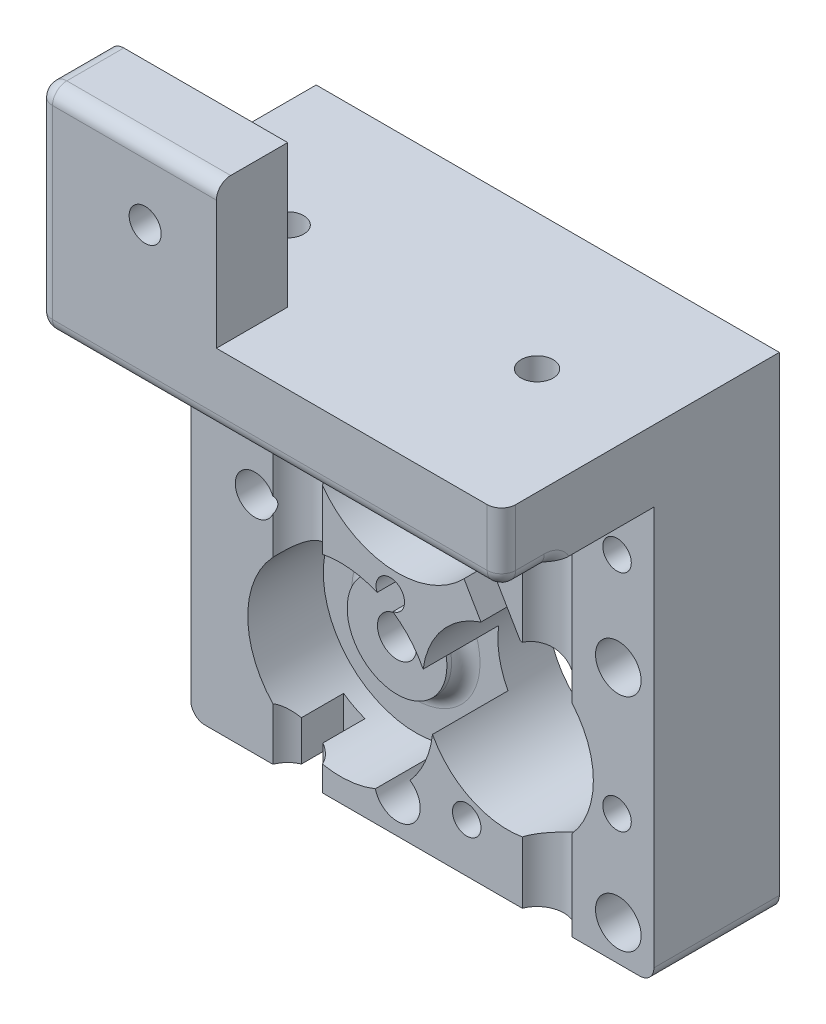
SolidWorks part; units mm, degrees
ref_plane "Front Plane" through (0, 0, 0) normal (0, 0, 1) x (1, 0, 0)
ref_plane "Top Plane" through (0, 0, 0) normal (0, 1, 0) x (1, 0, 0)
ref_plane "Right Plane" through (0, 0, 0) normal (1, 0, 0) x (0, 0, -1)
sketch "Sketch1" plane through (0, 0, 0) normal (0, 0, 1) x (1, 0, 0)
  line L1 (-44.5, 47.5) -> (20.5, 47.5)
  line L2 (-44.5, 47.5) -> (-44.5, -20.5)
  line L3 (-44.5, -20.5) -> (20.5, -20.5)
  line L4 (20.5, 47.5) -> (20.5, -20.5)
  circle A0 centre (0, 0) radius 12
  circle A1 centre (-15.5, 15.5) radius 1.75
  circle A2 centre (15.5, 15.5) radius 1.75
  circle A3 centre (15.5, -15.5) radius 1.75
  circle A4 centre (-15.5, -15.5) radius 1.75
  circle A6 centre (-15.5, 24.5) radius 2.75
  dimension "D1" = 24
  dimension "D2" = 31
  dimension "D3" = 31
  dimension "D4" = 31
  dimension "D5" = 31
  dimension "D6" = 15.5
  dimension "D7" = 15.5
  dimension "D8" = 0
  dimension "D9" = 3.5
  dimension "D10" = 3.5
  dimension "D11" = 3.5
  dimension "D12" = 3.5
  dimension "D13" = 23
  dimension "D14" = 29
  dimension "D16" = 5.5
  dimension "D21" = 47.5
  dimension "D22" = 44.5
  dimension "D19" = 65
  dimension "D20" = 68
extrude "Boss-Extrude1" add sketch "Sketch1" along normal blind 7
sketch "Sketch2" plane through (0, 0, 7) normal (0, 0, 1) x (1, 0, 0)
  line L0 (20.5, 47.5) -> (-44.5, 47.5) construction
  line L1 (-44.5, 47.5) -> (-44.5, -20.5) construction
  circle A0 centre (-15.5, 24.5) radius 2.75
  circle A6 centre (-35.5, 11) radius 2.75
  circle A8 centre (-23.5, -4.2471) radius 2.75
  circle A9 centre (-23.5, -4.2471) radius 7
  circle A10 centre (-15.5, 24.5) radius 7
  circle A11 centre (-35.5, 11) radius 4
  dimension "D1" = 14
  dimension "D2" = 5.5
  dimension "D3" = 5.5
  dimension "D4" = 8
  dimension "D6" = 14
  dimension "D5" = 23
  dimension "D8" = 29
  dimension "D9" = 36.5
  dimension "D10" = 9
  dimension "D11" = 51.7471
  dimension "D7" = 21
extrude "Boss-Extrude2" add sketch "Sketch2" along normal blind 2.65
sketch "Sketch3" plane through (20.5, 0, 0) normal (1, 0, 0) x (0, 0, -1)
  line L1 (-7, 47.5) -> (-29, 47.5)
  line L2 (-7, 47.5) -> (-7, 37.5)
  line L3 (-7, 37.5) -> (-29, 37.5)
  line L4 (-29, 47.5) -> (-29, 37.5)
  line L5 (-29, 37.5) -> (-39, 37.5)
  line L6 (-29, 37.5) -> (-29, 67.5)
  line L7 (-29, 67.5) -> (-39, 67.5)
  line L8 (-39, 37.5) -> (-39, 67.5)
  line M7 (-7, 47.5) -> (-7, -20.5)
  dimension "D1" = 22
  dimension "D2" = 10
  dimension "D3" = 20
  dimension "D4" = 10
extrude "Boss-Extrude3" add sketch "Sketch3" against normal through all contours L1 L4 L3 M7 | L8 L5 L4 L6 L7 region at (20.5, 42.5, 18) region at (20.5, 52.5, 34)
sketch "Sketch4" plane through (0, 0, 39) normal (0, 0, 1) x (1, 0, 0)
  line L0 (-44.5, 37.5) -> (20.5, 37.5) construction
  line L1 (-44.5, 67.5) -> (20.5, 67.5) construction
  line L2 (-44.5, 37.5) -> (-44.5, 67.5) construction
  line L3 (20.5, 37.5) -> (20.5, 67.5) construction
  circle A0 centre (-29.5, 57.5) radius 2.25
  circle A1 centre (5.5, 57.5) radius 2.25
  dimension "D1" = 4.5
  dimension "D2" = 20
  dimension "D3" = 10
  dimension "D4" = 15
  dimension "D5" = 10
  dimension "D6" = 15
  dimension "D7" = 4.5
extrude "Cut-Extrude1" cut sketch "Sketch4" against normal blind 10
sketch "Sketch5" plane through (0, 37.5, 0) normal (0, -1, 0) x (1, 0, 0)
  line L0 (-44.5, 7) -> (-44.5, 39) construction
  line L1 (-44.5, 39) -> (20.5, 39) construction
  line L2 (20.5, 7) -> (20.5, 39) construction
  circle A0 centre (-29.5, 19) radius 2.25
  circle A1 centre (5.5, 19) radius 2.25
  dimension "D1" = 15
  dimension "D2" = 20
  dimension "D3" = 20
  dimension "D4" = 15
  dimension "D5" = 4.5
  dimension "D6" = 4.5
extrude "Cut-Extrude2" cut sketch "Sketch5" against normal blind 10
sketch "Sketch7" plane through (0, 0, 0) normal (0, 0, -1) x (-1, 0, 0)
  line L1 (-20.5, -20.5) -> (20.5, -20.5)
  line L2 (-20.5, -20.5) -> (-20.5, 20.5)
  line L3 (-20.5, 20.5) -> (20.5, 20.5)
  line L4 (20.5, -20.5) -> (20.5, 20.5)
  circle A0 centre (0, 0) radius 12
  circle A1 centre (-15.5, 15.5) radius 1.75
  circle A2 centre (15.5, 15.5) radius 1.75
  circle A3 centre (15.5, -15.5) radius 1.75
  circle A4 centre (-15.5, -15.5) radius 1.75
  dimension "D2" = 5
  dimension "D3" = 5
  dimension "D4" = 5
  dimension "D1" = 5
extrude "Boss-Extrude5" add sketch "Sketch7" along normal blind 5.9
sketch "Sketch8" plane through (0, 0, 9.65) normal (0, 0, 1) x (1, 0, 0)
  circle A0 centre (-35.5, 11) radius 2.75
  circle A1 centre (-35.5, 11) radius 4
  dimension "D1" = 8
extrude "Boss-Extrude6" add sketch "Sketch8" along normal blind 7.95
sketch "Sketch10" plane through (0, 0, 7) normal (0, 0, 1) x (1, 0, 0)
  circle A0 centre (-35.5, 11) radius 2.75
  circle A1 centre (-23.5, -4.2471) radius 2.75
extrude "Cut-Extrude3" cut sketch "Sketch10" against normal blind 9.45
sketch "Sketch11" plane through (0, 0, 7) normal (0, 0, 1) x (1, 0, 0)
  line L1 (-44.5, 37.5) -> (20.5, 37.5)
  line L2 (-44.5, 37.5) -> (-44.5, -20.5)
  line L3 (-44.5, -20.5) -> (20.5, -20.5)
  line L4 (20.5, 37.5) -> (20.5, -20.5)
  circle A0 centre (-23.5, -4.2471) radius 10
  circle A1 centre (-15.5, 24.5) radius 10
  circle A2 centre (-15.5, 24.5) radius 2.75
  circle A3 centre (-23.5, -4.2471) radius 2.75
  circle A4 centre (0, 0) radius 7.25
  circle M1 centre (15.5, -15.5) radius 1.75
  circle M2 centre (-15.5, 15.5) radius 1.75
  circle M3 centre (0, 0) radius 12
  circle M4 centre (15.5, 15.5) radius 1.75
  circle M5 centre (-15.5, -15.5) radius 1.75
  circle M7 centre (-35.5, 11) radius 4
  line M9 (20.5, -20.5) -> (20.5, 37.5)
  line M10 (20.5, 37.5) -> (-44.5, 37.5)
  line M11 (-44.5, 37.5) -> (-44.5, -20.5)
  line M12 (-44.5, -20.5) -> (20.5, -20.5)
  dimension "D1" = 20
  dimension "D2" = 20
  dimension "D3" = 14.5
extrude "Boss-Extrude7" add sketch "Sketch11" along normal blind 10 contours A1 A0 M12 M9 M10 M11 M2 M4 M7 M5 M3 M1 | A4 M3 region at (-12.0095, 9.6819, 7) region at (-11.6606, 0, 7)
sketch "Sketch12" plane through (0, 0, 17) normal (0, 0, 1) x (1, 0, 0)
  line L1 (-11.6164, 26.7733) -> (3.0206, 1.7681)
  line L2 (-44.5, 37.5) -> (-44.5, -20.5) construction
  line L6 (-44.5, -20.5) -> (20.5, -20.5) construction
  line L7 (-44.5, 29) -> (-15.5, 29)
  line L8 (-44.5, 29) -> (-44.5, 32)
  line L9 (-44.5, 32) -> (-15.5, 32)
  line L13 (-9.0274, 28.2888) -> (5.6096, 3.2836)
  line L14 (-21.2843, 2.9181) -> (-1.034, -3.3438)
  line L17 (-22.1706, 0.052) -> (-1.9202, -6.2099)
  line L18 (-31, -4.2471) -> (-31, -20.5)
  line L20 (-31, -20.5) -> (-28, -20.5)
  line L21 (-28, -4.2471) -> (-28, -20.5)
  arc A5 (-21.2843, 2.9181) -> (-31, -4.2471) centre (-23.5, -4.2471) ccw
  arc A6 (-22.1706, 0.052) -> (-28, -4.2471) centre (-23.5, -4.2471) ccw
  arc A7 (-1.034, -3.3438) -> (3.0206, 1.7681) centre (0, 0) ccw
  arc A8 (-11.6164, 26.7733) -> (-15.5, 29) centre (-15.5, 24.5) ccw
  arc A9 (-9.0274, 28.2888) -> (-15.5, 32) centre (-15.5, 24.5) ccw
  arc A10 (-1.9202, -6.2099) -> (5.6096, 3.2836) centre (0, 0) ccw
  dimension "D4" = 3
  dimension "D5" = 3
  dimension "D6" = 3
  dimension "D7" = 3
extrude "Cut-Extrude4" cut sketch "Sketch12" against normal up to surface (7.35 mm away) up to face at (-16.5, -4.2471, 9.65)
sketch "Sketch13" plane through (0, 0, 17) normal (0, 0, 1) x (1, 0, 0)
  line L0 (-44.5, 29) -> (-44.5, -20.5) construction
  line L1 (-15.5, 34.5) -> (-44.5, 34.5)
  line L3 (-15.5, 14.5) -> (-44.5, 14.5)
  line L4 (-44.5, 34.5) -> (-44.5, 14.5)
  line L11 (-23.5, 5.7529) -> (-44.5, 5.7529)
  line L13 (-23.5, -14.2471) -> (-44.5, -14.2471)
  line L14 (-44.5, 5.7529) -> (-44.5, -14.2471)
  arc A0 (-15.5, 14.5) -> (-15.5, 34.5) centre (-15.5, 24.5) ccw
  circle A1 centre (-15.5, 24.5) radius 7
  circle A2 centre (-23.5, -4.2471) radius 7
  arc A4 (-23.5, -14.2471) -> (-23.5, 5.7529) centre (-23.5, -4.2471) ccw
extrude "Cut-Extrude5" cut sketch "Sketch13" against normal up to surface (10 mm away) up to face at (-15.5, 25.875, 7)
sketch "Sketch14" plane through (0, 0, 17) normal (0, 0, 1) x (1, 0, 0)
  circle A0 centre (15.5, 15.5) radius 3
  circle A1 centre (15.5, -15.5) radius 3
  circle A2 centre (-15.5, -15.5) radius 3
  circle A3 centre (-15.5, 15.5) radius 3
  dimension "D1" = 6
extrude "Cut-Extrude6" cut sketch "Sketch14" against normal blind 17
sketch "Sketch15" plane through (0, 0, 17) normal (0, 0, 1) x (1, 0, 0)
  line L0 (-44.5, 37.5) -> (20.5, 37.5)
  line L1 (20.5, 37.5) -> (20.5, -20.5)
  line L8 (-26.9872, 5.7529) -> (-23.5, 5.7529)
  line L9 (-26.1325, 14.5) -> (-18.3284, 14.5)
  line L10 (-15.5, 34.5) -> (-44.5, 34.5)
  line L11 (-44.5, 34.5) -> (-44.5, 37.5)
  line L12 (-14.9652, 0.9641) -> (-7.0998, -1.4681)
  line L13 (-4.9882, -5.2612) -> (-13.6389, -2.5862)
  line L14 (3.9873, 6.055) -> (-5.686, 22.5805)
  line L15 (-7.1051, 19.0663) -> (-0.1869, 7.2476)
  line L18 (-28, -20.5) -> (-28, -14.2471)
  line L19 (-28, -14.2471) -> (-23.5, -14.2471)
  line L21 (-44.5, -20.5) -> (-31, -20.5)
  line L22 (-44.5, -20.5) -> (-44.5, -14.2471)
  line L23 (-44.5, -14.2471) -> (-31, -14.2471)
  line L24 (-31, -20.5) -> (-31, -14.2471)
  line L25 (-28, -20.5) -> (20.5, -20.5)
  arc A0 (-12.5519, 14.9444) -> (-7.1051, 19.0663) centre (-15.5, 24.5) ccw
  arc A1 (-18.3284, 14.5) -> (-12.5519, 14.9444) centre (-15.5, 15.5) ccw
  arc A4 (-4.9882, -5.2612) -> (3.9873, 6.055) centre (0, 0) ccw
  circle A5 centre (15.5, 15.5) radius 3
  circle A6 centre (15.5, -15.5) radius 3
  arc A8 (-0.1869, 7.2476) -> (-7.0998, -1.4681) centre (0, 0) ccw
  arc A12 (-5.686, 22.5805) -> (-15.5, 34.5) centre (-15.5, 24.5) ccw
  circle A15 centre (-15.5, -15.5) radius 3
  arc A18 (-14.9652, 0.9641) -> (-23.5, 5.7529) centre (-23.5, -4.2471) ccw
  arc A19 (-26.9872, 5.7529) -> (-26.1325, 14.5) centre (-35.5, 11) ccw
  arc A20 (-23.5, -14.2471) -> (-13.6389, -2.5862) centre (-23.5, -4.2471) ccw
extrude "Boss-Extrude9" add sketch "Sketch15" along normal blind 3.5
sketch "Sketch16" plane through (0, 0, 20.5) normal (0, 0, 1) x (1, 0, 0)
  line L1 (-44.5, 37.5) -> (20.5, 37.5)
  line L2 (-44.5, 37.5) -> (-44.5, -20.5)
  line L3 (-44.5, -20.5) -> (20.5, -20.5)
  line L4 (20.5, 37.5) -> (20.5, -20.5)
  arc A0 (-44.5, 6.6411) -> (-44.5, 15.3589) centre (-35.5, 11) ccw
  circle A1 centre (-15.5, 15.5) radius 3
  circle A2 centre (15.5, 15.5) radius 3
  circle A3 centre (15.5, -15.5) radius 3
  circle A4 centre (-15.5, -15.5) radius 3
  circle M1 centre (15.5, -15.5) radius 3
  line M2 (-44.5, 37.5) -> (-44.5, 34.5)
  line M3 (-44.5, 34.5) -> (-15.5, 34.5)
  arc M4 (-15.5, 34.5) -> (-5.686, 22.5805) centre (-15.5, 24.5) cw
  line M5 (-5.686, 22.5805) -> (3.9873, 6.055)
  arc M6 (3.9873, 6.055) -> (-4.9882, -5.2612) centre (0, 0) cw
  line M7 (-4.9882, -5.2612) -> (-13.6389, -2.5862)
  arc M8 (-13.6389, -2.5862) -> (-23.5, -14.2471) centre (-23.5, -4.2471) cw
  line M9 (-23.5, -14.2471) -> (-28, -14.2471)
  line M10 (-28, -14.2471) -> (-28, -20.5)
  line M11 (-28, -20.5) -> (20.5, -20.5)
  line M12 (20.5, -20.5) -> (20.5, 37.5)
  line M13 (20.5, 37.5) -> (7.1771, 37.5)
  line M14 (7.1771, 37.5) -> (3.8229, 37.5)
  line M15 (3.8229, 37.5) -> (-27.8229, 37.5)
  line M16 (-27.8229, 37.5) -> (-31.1771, 37.5)
  line M17 (-31.1771, 37.5) -> (-44.5, 37.5)
  circle M18 centre (15.5, 15.5) radius 3
  circle M19 centre (-15.5, -15.5) radius 3
extrude "Boss-Extrude10" add sketch "Sketch16" along normal blind 7.5 contours A0 L2 L3 A1 M10 M9 M8 M7 M6 M5 M4 M3 | M17 M2 M3 M4 M5 M6 M7 M8 M9 M10 M11 M12 M13 M14 M15 M16 M19 M18 M1 region at (2.7798, 8.7673, 20.5) region at (-21.9314, 8.3685, 20.5)
sketch "Sketch17" plane through (0, 0, 28) normal (0, 0, 1) x (1, 0, 0)
  line L1 (-44.5, 37.5) -> (20.5, 37.5)
  line L2 (-44.5, 37.5) -> (-44.5, -20.5)
  line L3 (-44.5, -20.5) -> (20.5, -20.5)
  line L4 (20.5, 37.5) -> (20.5, -20.5)
  circle A0 centre (-15.5, 15.5) radius 3
  circle A1 centre (15.5, 15.5) radius 3
  circle A2 centre (15.5, -15.5) radius 3
  circle A3 centre (-15.5, -15.5) radius 3
extrude "Boss-Extrude11" add sketch "Sketch17" along normal blind 3
sketch "Sketch18" plane through (0, 47.5, 0) normal (0, 1, 0) x (1, 0, 0)
  circle A0 centre (-29.5, -19) radius 2.25
  circle A1 centre (5.5, -19) radius 2.25
extrude "Cut-Extrude7" cut sketch "Sketch18" against normal through all
sketch "Sketch19" plane through (0, -20.5, 0) normal (0, -1, 0) x (1, 0, 0)
  circle A0 centre (-29.5, 19) radius 3.75
  circle A1 centre (5.5, 19) radius 3.75
  dimension "D1" = 7.5
  dimension "D2" = 7.5
extrude "Cut-Extrude8" cut sketch "Sketch19" against normal blind 58
fillet "Fillet2" radius 2 14 edges at (20.5, 37.5, 35) (-44.5, 37.5, 35) (-44.5, 67.5, 34) (20.5, 67.5, 34) (-12, 67.5, 39) (20.5, 52.5, 39) (-44.5, 52.5, 39) (-12, 37.5, 31) (-12, 37.5, 39) (20.5, 8.5, 31) (20.5, -20.5, 12.55) (-12, -20.5, 31) (-44.5, -20.5, 15.5) (-44.5, 8.5, 31)
sketch "Sketch20" plane through (0, 0, 0) normal (0, 0, -1) x (-1, 0, 0)
  line L0 (20.5, 20.5) -> (-20.5, 20.5) construction
  line L1 (13.1906, 28.5) -> (10.8812, 24.5)
  line L2 (10.8812, 24.5) -> (13.1906, 20.5)
  line L3 (13.1906, 20.5) -> (17.8094, 20.5)
  line L4 (17.8094, 20.5) -> (20.1188, 24.5)
  line L5 (20.1188, 24.5) -> (17.8094, 28.5)
  line L6 (17.8094, 28.5) -> (13.1906, 28.5)
  line L7 (39.5, 13.3094) -> (35.5, 15.6188)
  line L8 (35.5, 15.6188) -> (31.5, 13.3094)
  line L9 (31.5, 13.3094) -> (31.5, 8.6906)
  line L10 (31.5, 8.6906) -> (35.5, 6.3812)
  line L11 (35.5, 6.3812) -> (39.5, 8.6906)
  line L12 (39.5, 8.6906) -> (39.5, 13.3094)
  line L13 (23.5, 0.3717) -> (19.5, -1.9377)
  line L14 (19.5, -1.9377) -> (19.5, -6.5565)
  line L15 (19.5, -6.5565) -> (23.5, -8.8659)
  line L16 (23.5, -8.8659) -> (27.5, -6.5565)
  line L17 (27.5, -6.5565) -> (27.5, -1.9377)
  line L18 (27.5, -1.9377) -> (23.5, 0.3717)
  line L19 (20.5, -20.5) -> (20.5, 20.5) construction
  line L20 (20.5, -20.5) -> (20.5, 20.5) construction
  circle A0 centre (15.5, 24.5) radius 4 construction
  circle A1 centre (35.5, 11) radius 4 construction
  circle A2 centre (23.5, -4.2471) radius 4 construction
  point P33 (33.5, 14.4641)
  dimension "D1" = 8
extrude "Cut-Extrude9" cut sketch "Sketch20" against normal blind 5.5
sketch "Sketch21" plane through (0, 0, 0) normal (0, 0, -1) x (-1, 0, 0)
  line L1 (17.9537, 28.75) -> (13.0463, 28.75)
  line L2 (13.0463, 28.75) -> (10.5925, 24.5)
  line L3 (10.5925, 24.5) -> (13.0463, 20.25)
  line L4 (13.0463, 20.25) -> (17.9537, 20.25)
  line L5 (17.9537, 20.25) -> (20.4075, 24.5)
  line L6 (20.4075, 24.5) -> (17.9537, 28.75)
  line L7 (27.75, -1.7934) -> (23.5, 0.6603)
  line L8 (23.5, 0.6603) -> (19.25, -1.7934)
  line L9 (19.25, -1.7934) -> (19.25, -6.7009)
  line L10 (19.25, -6.7009) -> (23.5, -9.1546)
  line L11 (23.5, -9.1546) -> (27.75, -6.7009)
  line L12 (27.75, -6.7009) -> (27.75, -1.7934)
  circle A0 centre (15.5, 24.5) radius 4.25 construction
  circle A1 centre (23.5, -4.2471) radius 4.25 construction
extrude "Cut-Extrude10" cut sketch "Sketch21" along normal blind 29.5
sketch "Sketch22" plane through (0, 0, 39) normal (0, 0, 1) x (1, 0, 0)
  line L0 (-44.5, 35.5) -> (-44.5, -20.5) construction
  line L1 (18.5, -20.5) -> (-44.5, -20.5) construction
  line L2 (20.5, 35.5) -> (20.5, 39.5) construction
  line L3 (-44.5, -20.5) -> (20.5, -20.5)
  line L4 (-44.5, -20.5) -> (-44.5, 37.5)
  line L5 (-44.5, 37.5) -> (20.5, 37.5)
  line L6 (20.5, -20.5) -> (20.5, 37.5)
extrude "Cut-Extrude11" cut sketch "Sketch22" against normal up to surface (21.4 mm away) up to face at (-35.9269, 11, 17.6)
sketch "Sketch23" plane through (0, 0, 17.6) normal (0, 0, 1) x (1, 0, 0)
  line L0 (20.5, 37.5) -> (20.5, -18.5) construction
  circle A0 centre (-5.7708, -13.6227) radius 1.8
  circle A1 centre (-16.5, 8.4364) radius 1.8
  circle A2 centre (15.3222, 29.1269) radius 1.8
  circle A3 centre (15.3222, -2.3516) radius 1.8
  dimension "D1" = 3.6
  dimension "D2" = 37
extrude "Cut-Extrude12" cut sketch "Sketch23" against normal blind 10
sketch "Sketch24" plane through (0, 0, 17.6) normal (0, 0, 1) x (1, 0, 0)
  circle A0 centre (-16.5, 8.4364) radius 2
  circle A1 centre (15.3222, 29.1269) radius 2
  circle A2 centre (15.3222, -2.3516) radius 2
  circle A3 centre (-5.7708, -13.6227) radius 2
  dimension "D1" = 4
extrude "Cut-Extrude13" cut sketch "Sketch24" against normal blind 4
sketch "Sketch26" plane through (0, 0, -5.9) normal (0, 0, -1) x (-1, 0, 0)
  line L1 (-20.5, 20.5) -> (20.5, 20.5)
  line L2 (-20.5, 20.5) -> (-20.5, -20.5)
  line L3 (-20.5, -20.5) -> (20.5, -20.5)
  line L4 (20.5, 20.5) -> (20.5, -20.5)
extrude "Cut-Extrude14" cut sketch "Sketch26" against normal up to surface (5.9 mm away) up to face at (-18.2276, 9.3731, 0)
sketch "Sketch27" plane through (0, 0, 17) normal (0, 0, 1) x (1, 0, 0)
  line L1 (-44.5, 14.5) -> (-18.3284, 14.5)
  line L2 (-44.5, 14.5) -> (-44.5, 30.5)
  line L3 (-44.5, 30.5) -> (-23.5, 30.5)
  line L5 (-44.5, 34.5) -> (-32.9789, 34.5) construction
  line L6 (-31, -14.2471) -> (-31, -10.8615)
  line L7 (-44.5, -14.2471) -> (-31, -14.2471)
  line L8 (-44.5, -14.2471) -> (-44.5, 5.7529)
  line L9 (-44.5, 5.7529) -> (-23.5, 5.7529)
  arc A0 (-23.5, 5.7529) -> (-31, -10.8615) centre (-23.5, -4.2471) ccw
  arc A1 (-23.5, 30.5) -> (-18.4481, 14.9444) centre (-15.5, 24.5) ccw
  arc A2 (-18.4481, 14.9444) -> (-18.3284, 14.5) centre (-15.5, 15.5) ccw
  dimension "D1" = 4
extrude "Boss-Extrude12" add sketch "Sketch27" against normal up to surface (10 mm away) and the other way up to surface (0.6 mm away) up to face at (-31.5, -4.2471, 7) other way up to face at (-35.9269, 11, 17.6)
sketch "Sketch29" plane through (0, 0, 17) normal (0, 0, 1) x (1, 0, 0)
  line L0 (-33.5635, 14.5) -> (-32.6721, 14.5)
  line L1 (-44.5, 5.7529) -> (-32.6721, 5.7529)
  line L2 (-44.5, 5.7529) -> (-44.5, 14.5)
  line L3 (-44.5, 14.5) -> (-37.4365, 14.5)
  line L4 (-32.6721, 5.7529) -> (-32.6721, 8.171)
  line L5 (-26.3279, 14.5) -> (-26.1325, 14.5)
  line L6 (-26.3279, 14.5) -> (-26.3279, 7.0161)
  line L9 (-32.6721, 13.829) -> (-32.6721, 14.5)
  arc A0 (-37.4365, 14.5) -> (-32.6721, 8.171) centre (-35.5, 11) ccw
  arc A1 (-26.3279, 7.0161) -> (-26.1325, 14.5) centre (-35.5, 11) ccw
  arc A2 (-32.6721, 13.829) -> (-33.5635, 14.5) centre (-35.5, 11) ccw
extrude "Boss-Extrude13" add sketch "Sketch29" along normal up to surface (0.6 mm away) up to face at (-29.2401, 6.0247, 17.6)
sketch "Sketch28" plane through (0, -20.5, 0) normal (0, -1, 0) x (1, 0, 0)
  circle A0 centre (-29.5, 19) radius 3.75
extrude "Cut-Extrude15" cut sketch "Sketch28" against normal up to surface (58 mm away) up to face at (-29.5, 37.5, 16.75)
ref_plane "Plane2" through (0, 0, 27.6) normal (0, 0, 1) x (1, 0, 0)
sketch "Sketch31" plane through (0, 0, 27.6) normal (0, 0, 1) x (1, 0, 0)
  line L0 (-44.5, 34.5) -> (-32.9789, 34.5) construction
  line L1 (-32.9789, 34.5) -> (-32.9789, 37.5) construction
  line L2 (-32.9789, 37.5) -> (-44.5, 37.5) construction
  line L3 (-44.5, 37.5) -> (-44.5, 34.5) construction
  line L4 (-26.0211, 30.5) -> (-26.0211, 5.4298) construction
  line L5 (-14.9652, 0.9641) -> (-7.0998, -1.4681) construction
  line L6 (-0.1869, 7.2476) -> (-7.1051, 19.0663) construction
  line L7 (-23.5, 30.5) -> (-26.0211, 30.5) construction
  line L8 (-26.0211, 37.5) -> (-26.0211, 34.5) construction
  line L9 (-26.0211, 34.5) -> (-15.5, 34.5) construction
  line L10 (-5.686, 22.5805) -> (2.0211, 9.414) construction
  line L11 (2.0211, 9.414) -> (2.0211, 37.5) construction
  line L12 (2.0211, 37.5) -> (-26.0211, 37.5) construction
  line L13 (8.9789, 37.5) -> (8.9789, -20.5) construction
  line L14 (8.9789, -20.5) -> (18.5, -20.5) construction
  line L15 (20.5, -18.5) -> (20.5, 37.5) construction
  line L16 (20.5, 37.5) -> (8.9789, 37.5) construction
  line L17 (-26.0211, -14.2471) -> (-26.0211, -20.5) construction
  line L18 (-26.0211, -20.5) -> (2.0211, -20.5) construction
  line L19 (2.0211, -20.5) -> (2.0211, -6.9626) construction
  line L20 (-4.9882, -5.2612) -> (-13.6389, -2.5862) construction
  line L21 (-23.5, -14.2471) -> (-26.0211, -14.2471) construction
  line L22 (-32.9789, 12.0984) -> (-32.9789, 30.5) construction
  line L23 (-32.9789, 30.5) -> (-44.5, 30.5) construction
  line L24 (-44.5, 30.5) -> (-44.5, -18.5) construction
  line L25 (-42.5, -20.5) -> (-32.9789, -20.5) construction
  line L26 (-32.9789, -20.5) -> (-32.9789, -7.4332) construction
  line L27 (-32.9789, -1.0611) -> (-32.9789, 9.9016) construction
  line L28 (-44.5, 34.5) -> (-32.9789, 34.5)
  line L29 (-32.9789, 34.5) -> (-32.9789, 37.5)
  line L30 (-32.9789, 37.5) -> (-44.5, 37.5)
  line L31 (-44.5, 37.5) -> (-44.5, 34.5)
  line L32 (-26.0211, 30.5) -> (-26.0211, 5.4298)
  line L33 (-14.9652, 0.9641) -> (-7.0998, -1.4681)
  line L34 (-0.1869, 7.2476) -> (-7.1051, 19.0663)
  line L35 (-23.5, 30.5) -> (-26.0211, 30.5)
  line L36 (-26.0211, 37.5) -> (-26.0211, 34.5)
  line L37 (-26.0211, 34.5) -> (-15.5, 34.5)
  line L38 (-5.686, 22.5805) -> (2.0211, 9.414)
  line L39 (2.0211, 9.414) -> (2.0211, 37.5)
  line L40 (2.0211, 37.5) -> (-26.0211, 37.5)
  line L41 (8.9789, 37.5) -> (8.9789, -20.5)
  line L42 (8.9789, -20.5) -> (18.5, -20.5)
  line L43 (20.5, -18.5) -> (20.5, 37.5)
  line L44 (20.5, 37.5) -> (8.9789, 37.5)
  line L45 (-26.0211, -14.2471) -> (-26.0211, -20.5)
  line L46 (-26.0211, -20.5) -> (2.0211, -20.5)
  line L47 (2.0211, -20.5) -> (2.0211, -6.9626)
  line L48 (-4.9882, -5.2612) -> (-13.6389, -2.5862)
  line L49 (-23.5, -14.2471) -> (-26.0211, -14.2471)
  line L50 (-32.9789, 12.0984) -> (-32.9789, 30.5)
  line L51 (-32.9789, 30.5) -> (-44.5, 30.5)
  line L52 (-44.5, 30.5) -> (-44.5, -18.5)
  line L53 (-42.5, -20.5) -> (-32.9789, -20.5)
  line L54 (-32.9789, -20.5) -> (-32.9789, -7.4332)
  line L55 (-32.9789, -1.0611) -> (-32.9789, 9.9016)
  arc A0 (-14.9652, 0.9641) -> (-26.0211, 5.4298) centre (-23.5, -4.2471) ccw construction
  arc A1 (-0.1869, 7.2476) -> (-7.0998, -1.4681) centre (0, 0) ccw construction
  arc A2 (-12.5519, 14.9444) -> (-7.1051, 19.0663) centre (-15.5, 24.5) ccw construction
  arc A3 (-18.4481, 14.9444) -> (-12.5519, 14.9444) centre (-15.5, 15.5) ccw construction
  arc A4 (-23.5, 30.5) -> (-18.4481, 14.9444) centre (-15.5, 24.5) ccw construction
  arc A5 (-5.686, 22.5805) -> (-15.5, 34.5) centre (-15.5, 24.5) ccw construction
  arc A6 (18.5, -20.5) -> (20.5, -18.5) centre (18.5, -18.5) ccw construction
  arc A7 (-4.9882, -5.2612) -> (2.0211, -6.9626) centre (0, 0) ccw construction
  arc A8 (-23.5, -14.2471) -> (-13.6389, -2.5862) centre (-23.5, -4.2471) ccw construction
  arc A9 (-44.5, -18.5) -> (-42.5, -20.5) centre (-42.5, -18.5) ccw construction
  arc A10 (-32.9789, -1.0611) -> (-32.9789, -7.4332) centre (-23.5, -4.2471) ccw construction
  arc A11 (-32.9789, 12.0984) -> (-32.9789, 9.9016) centre (-35.5, 11) ccw construction
  circle A12 centre (-5.7708, -13.6227) radius 2 construction
  circle A13 centre (-16.5, 8.4364) radius 2 construction
  circle A14 centre (15.3222, 29.1269) radius 2 construction
  circle A15 centre (15.3222, -2.3516) radius 2 construction
  arc A16 (-14.9652, 0.9641) -> (-26.0211, 5.4298) centre (-23.5, -4.2471) ccw
  arc A17 (-0.1869, 7.2476) -> (-7.0998, -1.4681) centre (0, 0) ccw
  arc A18 (-12.5519, 14.9444) -> (-7.1051, 19.0663) centre (-15.5, 24.5) ccw
  arc A19 (-18.4481, 14.9444) -> (-12.5519, 14.9444) centre (-15.5, 15.5) ccw
  arc A20 (-23.5, 30.5) -> (-18.4481, 14.9444) centre (-15.5, 24.5) ccw
  arc A21 (-5.686, 22.5805) -> (-15.5, 34.5) centre (-15.5, 24.5) ccw
  arc A22 (18.5, -20.5) -> (20.5, -18.5) centre (18.5, -18.5) ccw
  arc A23 (-4.9882, -5.2612) -> (2.0211, -6.9626) centre (0, 0) ccw
  arc A24 (-23.5, -14.2471) -> (-13.6389, -2.5862) centre (-23.5, -4.2471) ccw
  arc A25 (-44.5, -18.5) -> (-42.5, -20.5) centre (-42.5, -18.5) ccw
  arc A26 (-32.9789, -1.0611) -> (-32.9789, -7.4332) centre (-23.5, -4.2471) ccw
  arc A27 (-32.9789, 12.0984) -> (-32.9789, 9.9016) centre (-35.5, 11) ccw
  circle A28 centre (-5.7708, -13.6227) radius 2
  circle A29 centre (-16.5, 8.4364) radius 2
  circle A30 centre (15.3222, 29.1269) radius 2
  circle A31 centre (15.3222, -2.3516) radius 2
sketch "Sketch32" plane through (0, 0, 7) normal (0, 0, -1) x (-1, 0, 0)
  circle A0 centre (-15.5, 15.5) radius 3.2
  circle A1 centre (15.5, 15.5) radius 3.2
  circle A2 centre (15.5, -15.5) radius 3.2
  circle A3 centre (-15.5, -15.5) radius 3.2
  dimension "D1" = 6.4
extrude "Cut-Extrude16" cut sketch "Sketch32" against normal blind 14 and the other way blind 10
sketch "Sketch34" plane through (0, 0, 7) normal (0, 0, 1) x (1, 0, 0)
  circle A0 centre (-15.5, 24.5) radius 7
  circle A1 centre (-15.5, 24.5) radius 11
  circle A2 centre (-23.5, -4.2471) radius 7
  circle A3 centre (-23.5, -4.2471) radius 11
  dimension "D1" = 22
  dimension "D2" = 22
extrude "Cut-Extrude17" cut sketch "Sketch34" along normal up to surface (10.6 mm away) up to face at (-37.2866, 1.6213, 17.6)
sketch "Sketch35" plane through (0, 0, 7) normal (0, 0, -1) x (-1, 0, 0)
  circle A0 centre (0, 0) radius 12
extrude "Cut-Extrude18" cut sketch "Sketch35" against normal through all
fillet "Fillet4" radius 2 2 edges at (-16.5, -4.2471, 7) (-15.5, 31.5, 7)
sketch "Sketch36" plane through (0, 0, 0) normal (0, 0, -1) x (-1, 0, 0)
  circle A0 centre (-15.5, 15.5) radius 3.2
  circle A1 centre (-15.5, 15.5) radius 1.8
  circle A2 centre (15.5, 15.5) radius 3.2
  circle A3 centre (15.5, 15.5) radius 1.8
  circle A4 centre (15.5, -15.5) radius 3.2
  circle A5 centre (15.5, -15.5) radius 1.8
  circle A6 centre (-15.5, -15.5) radius 3.2
  circle A7 centre (-15.5, -15.5) radius 1.8
  dimension "D1" = 3.6
  dimension "D2" = 2
  dimension "D3" = 2
extrude "Boss-Extrude14" add sketch "Sketch36" against normal blind 6.5
sketch "Sketch37" plane through (0, 0, 29) normal (0, 0, -1) x (-1, 0, 0)
  line L0 (42.5, 67.5) -> (-18.5, 67.5) construction
  line L1 (-20.5, 47.5) -> (19.5, 47.5)
  line L2 (-20.5, 47.5) -> (-20.5, 67.5)
  line L3 (-20.5, 67.5) -> (19.5, 67.5)
  line L4 (19.5, 47.5) -> (19.5, 67.5)
  dimension "D1" = 40
extrude "Cut-Extrude19" cut sketch "Sketch37" against normal through all
sketch "Sketch38" plane through (0, 0, 17.6) normal (0, 0, 1) x (1, 0, 0)
  line L2 (-44.5, 34.5) -> (-44.5, 35.5)
  line L3 (-44.5, 35.5) -> (-22.4282, 35.5)
  line L6 (-44.5, 30.5) -> (-44.5, 29.5)
  line L7 (-44.5, 29.5) -> (-27.5, 29.5)
  line L10 (1.3427, 10.5731) -> (2.2057, 11.0783)
  line L11 (-3.1954, 20.3052) -> (2.2057, 11.0783)
  line L15 (-6.1547, 15.4631) -> (-2.9965, 10.0679)
  line L16 (-44.5, 30.5) -> (-44.5, 34.5)
  line L17 (1.3427, 10.5731) -> (-2.9965, 10.0679)
  arc A1 (-27.5, 29.5) -> (-6.1547, 15.4631) centre (-15.5, 24.5) ccw
  circle A2 centre (-23.5, -4.2471) radius 9
  circle A3 centre (-23.5, -4.2471) radius 13
  circle A4 centre (-15.5, 24.5) radius 9
  arc A5 (-12.7602, 13.8467) -> (-20.0826, 34.5) centre (-15.5, 24.5) ccw construction
  arc A6 (-13.5967, 0.5409) -> (-26.0211, 6.4601) centre (-23.5, -4.2471) ccw construction
  arc A8 (-3.1954, 20.3052) -> (-22.4282, 35.5) centre (-15.5, 24.5) ccw
  dimension "D1" = 2
  dimension "D2" = 2
  dimension "D3" = 1
  dimension "D4" = 1
  dimension "D5" = 1
extrude "Cut-Extrude20" cut sketch "Sketch38" against normal up to surface (10.6 mm away) up to face at (-14.5, -4.2471, 7)
